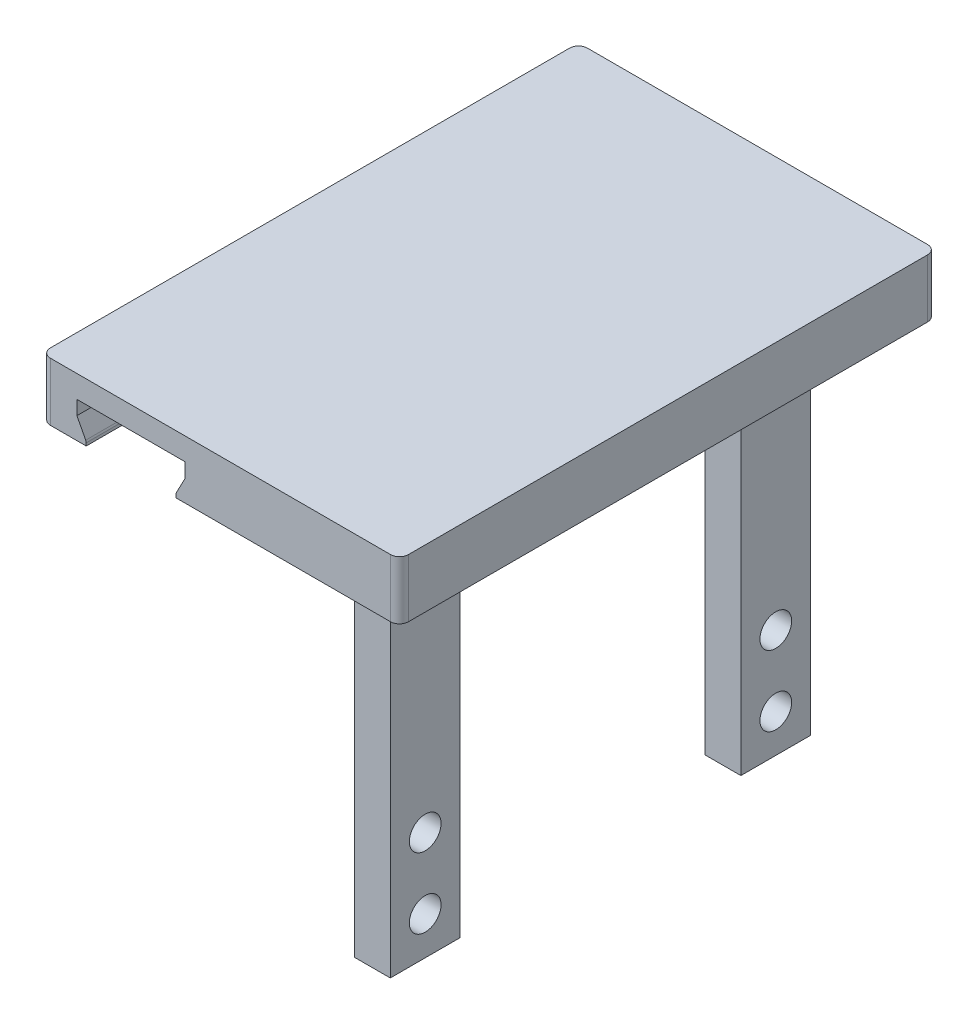
SolidWorks part; units mm, degrees
note: The reader was unsure of these and kept them because the rebuilt part matched: shared geometry of "Sketch2<5>", "Sketch2<6>".
ref_plane "Front Plane" through (0, 0, 0) normal (0, 0, 1) x (1, 0, 0)
ref_plane "Top Plane" through (0, 0, 0) normal (0, 1, 0) x (1, 0, 0)
ref_plane "Right Plane" through (0, 0, 0) normal (1, 0, 0) x (0, 0, -1)
sketch "Sketch2" plane through (0, 0, 0) normal (0, 1, 0) x (1, 0, 0)
  line L0 (0, 0) -> (0, -76.2)
  line L1 (0, -76.2) -> (50.8, -76.2)
  line L2 (50.8, -76.2) -> (50.8, 0)
  line L3 (50.8, 0) -> (0, 0)
  line L4 (0, -38.1) -> (6.35, -38.1)
  line L5 (6.35, -38.1) -> (19.0754, -38.1)
  line L6 (19.0754, -38.1) -> (36.139, -38.1)
  line L7 (36.139, -38.1) -> (36.139, -62.844)
  line L8 (36.139, -62.844) -> (41.219, -62.844)
  line L9 (41.219, -58.018) -> (36.139, -58.018)
  line L10 (36.139, -38.1) -> (36.139, -13.356)
  line L11 (36.139, -62.844) -> (36.139, -67.924)
  line L12 (36.139, -67.924) -> (41.219, -67.924)
  line L13 (41.219, -67.924) -> (41.219, -62.844)
  line L14 (36.139, -13.356) -> (41.219, -13.356)
  line L15 (41.219, -62.844) -> (41.219, -58.018)
  line L16 (41.219, -13.356) -> (41.219, -18.182)
  line L17 (41.219, -18.182) -> (36.139, -18.182)
  line L18 (41.219, -13.356) -> (41.219, -8.276)
  line L19 (36.139, -13.356) -> (36.139, -8.276)
  line L20 (36.139, -8.276) -> (41.219, -8.276)
  line L21 (6.35, -38.1) -> (6.35, 0)
  line L22 (6.35, -76.2) -> (6.35, -38.1)
  line L23 (19.0754, -38.1) -> (19.0754, -76.2)
  line L24 (19.0754, -38.1) -> (19.0754, 0)
  dimension "D1" = 76.2
  dimension "D2" = 50.8
  dimension "D3" = 6.35
  dimension "D4" = 12.7254
  dimension "D5" = 24.744
  dimension "D6" = 5.08
  dimension "D7" = 24.744
  dimension "D8" = 5.08
  dimension "D9" = 4.826
  dimension "D10" = 5.08
  dimension "D11" = 4.826
  dimension "D12" = 5.08
  dimension "D13" = 17.0636
extrude "Boss-Extrude1" add sketch "Sketch2" along normal blind 3.175
extrude "Boss-Extrude2" add sketch "Sketch2<5>" against normal blind 5.08
sketch "Sketch2<5>" plane through (0, 0, 0) normal (0, 1, 0) x (1, 0, 0) same geometry as "Sketch2"
extrude "Boss-Extrude3" add sketch "Sketch2<6>" against normal blind 57.15 contours L17 L16 L14 L10 | L20 L19 L14 L18 | L12 L13 L8 L11 | L8 L15 L9 L7
sketch "Sketch2<6>" plane through (0, 0, 0) normal (0, 1, 0) x (1, 0, 0) same geometry as "Sketch2"
sketch "Sketch4" plane through (36.139, 0, 0) normal (-1, 0, 0) x (0, 0, 1)
  line L0 (13.229, -57.15) -> (13.229, -46.7433) construction
  line L1 (18.182, -57.15) -> (8.276, -57.15) construction
  line L2 (13.229, -46.7433) -> (13.229, -41.7433)
  line L3 (13.229, -46.7433) -> (13.229, -51.7433)
  line L4 (58.018, -57.15) -> (67.924, -57.15) construction
  line L5 (62.971, -57.15) -> (62.971, -46.7433) construction
  line L6 (62.971, -46.7433) -> (62.971, -41.7433)
  line L7 (62.971, -46.7433) -> (62.971, -51.7433)
  circle A0 centre (13.229, -41.7433) radius 2.25
  circle A1 centre (13.229, -51.7433) radius 2.25
  circle A2 centre (62.971, -41.7433) radius 2.25
  circle A3 centre (62.971, -51.7433) radius 2.25
  dimension "D2" = 4.5
  dimension "D4" = 4.5
  dimension "D5" = 4.5
  dimension "D9" = 4.5
  dimension "D1" = 10.4067
  dimension "D3" = 5
  dimension "D6" = 10.4067
  dimension "D7" = 5
  dimension "D8" = 5
extrude "Cut-Extrude1" cut sketch "Sketch4" against normal blind 50.8
fillet "Fillet1" radius 1.27 12 edges at (0, -0.9525, 0) (0, -0.9525, 76.2) (50.8, -0.9525, 76.2) (50.8, -0.9525, 0) (38.679, -5.08, 67.924) (36.139, -5.08, 62.971) (38.679, -5.08, 58.018) (41.219, -5.08, 13.229) (36.139, -5.08, 13.229) (38.679, -5.08, 8.276) (41.219, -5.08, 62.971) (38.679, -5.08, 18.182)
sketch "Sketch5" plane through (0, 0, 0) normal (0, 0, -1) x (-1, 0, 0)
  line L0 (-19.0754, 0) -> (-20.3962, 0)
  line L1 (27.94, 0) -> (-27.94, 0) construction
  line L2 (-20.3962, 0) -> (-20.3962, -2.0066)
  line L3 (-19.0754, -2.0066) -> (-19.0754, -5.08)
  line L4 (-19.0754, -5.08) -> (-19.0754, 0) construction
  line L5 (-20.3962, -2.0066) -> (-19.0754, -2.0066)
  line L6 (-20.3962, -2.0066) -> (-19.0754, -4.532)
  line L7 (-19.0754, 0) -> (-19.0754, -2.0066)
  line L8 (-6.35, 0) -> (-5.0292, 0)
  line L10 (-5.0292, 0) -> (-5.0292, -2.0066)
  line L11 (-5.0292, -2.0066) -> (-6.35, -2.0066)
  line L12 (-6.35, -5.08) -> (-6.35, 0) construction
  line L13 (-6.35, -2.0066) -> (-6.35, -4.532)
  line L14 (-6.35, -4.532) -> (-5.0292, -2.0066)
  dimension "D1" = 1.3208
  dimension "D2" = 2.0066
  dimension "D3" = 1.3208
  dimension "D4" = 2.0066
extrude "Cut-Extrude2" cut sketch "Sketch5" against normal blind 101.6
fillet "Fillet2" radius 0.635 2 edges at (19.0754, -4.532, 38.1) (6.35, -4.532, 38.1)
